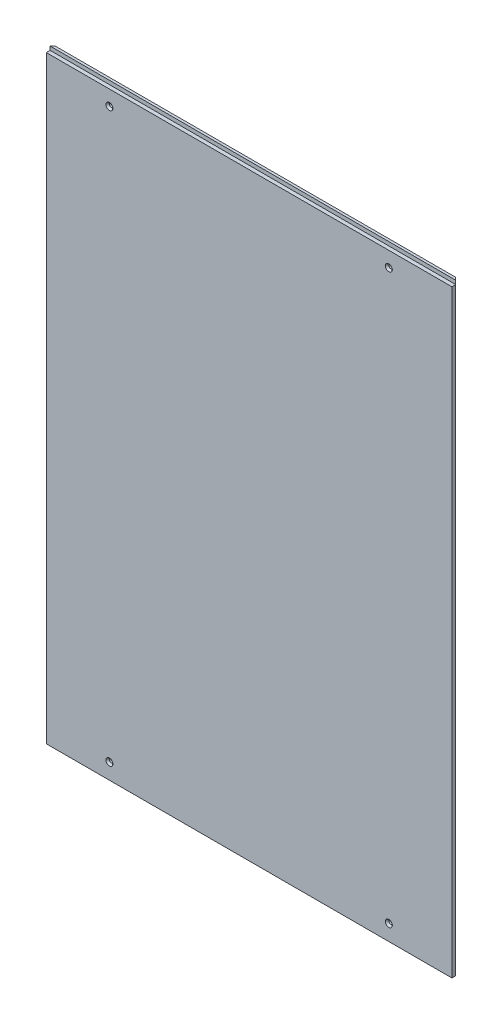
SolidWorks part; units mm, degrees
ref_plane "Front Plane" through (0, 0, 0) normal (0, 0, 1) x (1, 0, 0)
ref_plane "Top Plane" through (0, 0, 0) normal (0, 1, 0) x (1, 0, 0)
ref_plane "Right Plane" through (0, 0, 0) normal (1, 0, 0) x (0, 0, -1)
sketch "Sketch1" plane through (0, 0, 0) normal (0, 0, 1) x (1, 0, 0)
  line L1 (-321.5, -477.5) -> (321.5, -477.5)
  line L2 (-321.5, -477.5) -> (-321.5, 477.5)
  line L3 (-321.5, 477.5) -> (321.5, 477.5)
  line L4 (321.5, -477.5) -> (321.5, 477.5)
  line L5 (-321.5, -477.5) -> (321.5, 477.5) construction
  line L6 (-321.5, 477.5) -> (321.5, -477.5) construction
  point P0 (0, 0)
  dimension "ALTURA" = 955
  dimension "LARGURA" = 643
extrude "Boss-Extrude1" add sketch "Sketch1" along normal blind 10
sketch "Sketch2" plane through (-321.5, 0, 0) normal (-1, 0, 0) x (0, 0, 1)
  line L1 (10, 477.5) -> (4, 477.5)
  line L2 (10, 477.5) -> (10, 471.5)
  line L3 (10, 471.5) -> (4, 471.5)
  line L4 (4, 477.5) -> (4, 471.5)
  dimension "D1" = 6
  dimension "D2" = 6
extrude "Cut-Extrude1" cut sketch "Sketch2" against normal through all
chamfer "Chamfer1" distance 4 angle 45 2 edges at (321.5, 0, 0) (-321.5, 0, 0)
sketch "Sketch3" plane through (0, 0, 0) normal (0, 0, -1) x (-1, 0, 0)
  line L0 (-321.5, -477.5) -> (-321.5, 471.5) construction
  line L1 (317.5, -477.5) -> (-317.5, -477.5) construction
  line L2 (321.5, 471.5) -> (321.5, -477.5) construction
  line L3 (-317.5, 477.5) -> (317.5, 477.5) construction
  circle A0 centre (-221.5, -452.5) radius 2.6
  circle A1 centre (221.5, -452.5) radius 2.6
  circle A2 centre (221.5, 447.5) radius 2.6
  circle A3 centre (-221.5, 447.5) radius 2.6
  dimension "D1" = 5.2
  dimension "D2" = 100
  dimension "D3" = 25
  dimension "D4" = 100
  dimension "D5" = 30
extrude "Cut-Extrude2" cut sketch "Sketch3" against normal through all
chamfer "Chamfer2" distance 2.9 angle 45 4 edges at (-224.1, -452.5, 10) (218.9, -452.5, 10) (218.9, 447.5, 10) (-224.1, 447.5, 10)
sketch "Sketch4" plane through (0, 0, 0) normal (0, 0, -1) x (-1, 0, 0)
  line L0 (-317.5, 477.5) -> (317.5, 477.5) construction
  circle A0 centre (-241.5, 447.5) radius 6
  circle A1 centre (-201.5, 447.5) radius 6
  circle A2 centre (201.5, 447.5) radius 6
  circle A3 centre (241.5, 447.5) radius 6
  circle A5 centre (-221.5, 447.5) radius 2.6 construction
  circle A6 centre (221.5, 447.5) radius 2.6 construction
  dimension "D6" = 12
  dimension "D1" = 30
  dimension "D2" = 20
  dimension "D3" = 20
  dimension "D4" = 20
  dimension "D5" = 20
extrude "Cut-Extrude3" cut sketch "Sketch4" against normal blind 4
